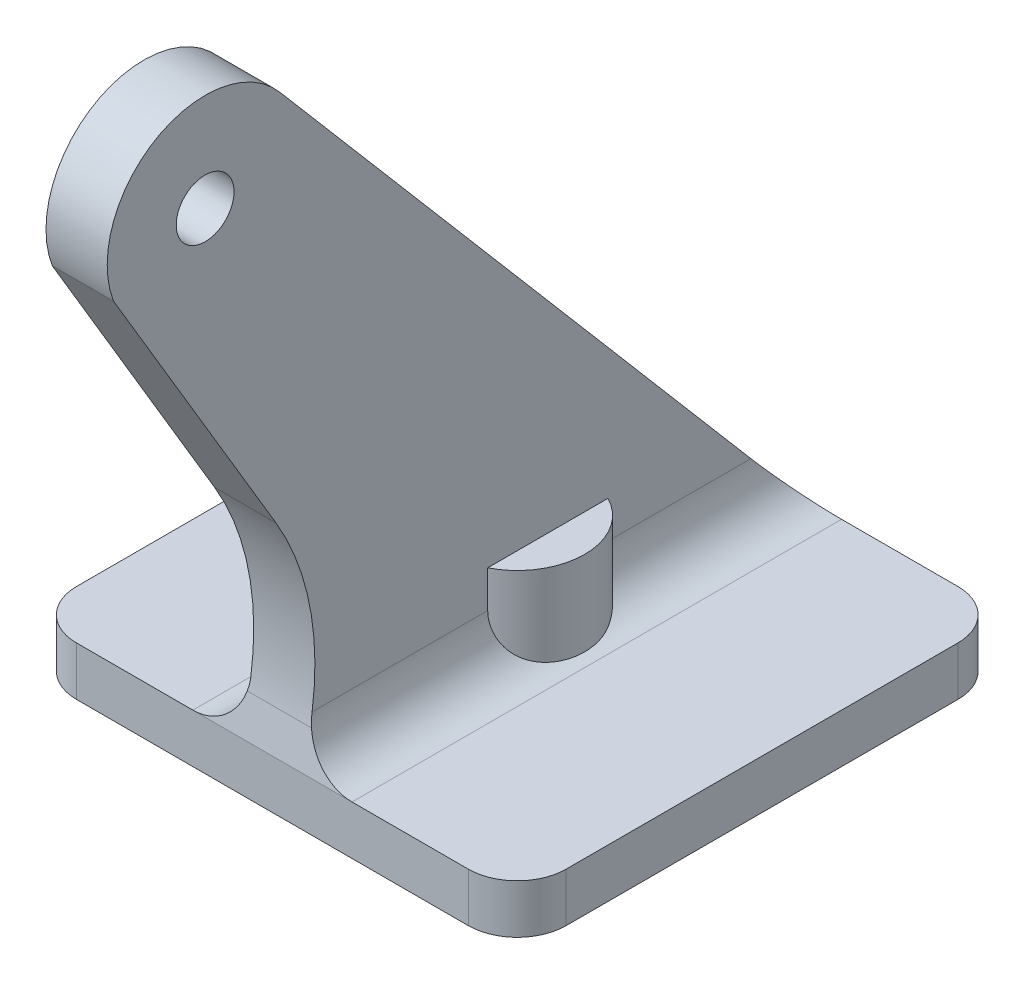
SolidWorks part; units mm, degrees
ref_plane "Front Plane" through (0, 0, 0) normal (0, 0, 1) x (1, 0, 0)
ref_plane "Top Plane" through (0, 0, 0) normal (0, 1, 0) x (1, 0, 0)
ref_plane "Right Plane" through (0, 0, 0) normal (1, 0, 0) x (0, 0, -1)
sketch "Sketch1" plane through (0, 0, 0) normal (0, 1, 0) x (1, 0, 0)
  line L1 (-12.7, 12.7) -> (12.7, 12.7)
  line L2 (-12.7, 12.7) -> (-12.7, -12.7)
  line L3 (-12.7, -12.7) -> (12.7, -12.7)
  line L4 (12.7, 12.7) -> (12.7, -12.7)
  line L5 (-12.7, 12.7) -> (12.7, -12.7) construction
  line L6 (-12.7, -12.7) -> (12.7, 12.7) construction
  point P0 (0, 0)
  dimension "D1" = 25.4
  dimension "D2" = 25.4
extrude "Boss-Extrude1" add sketch "Sketch1" along normal blind 2.54
sketch "Sketch3" plane through (0, 0, 0) normal (1, 0, 0) x (0, 0, -1)
  line L0 (-22.5349, 28.6918) -> (-14.1091, 14.5181)
  line L1 (-13.9132, 33.7746) -> (12.7, 2.54)
  line L2 (12.7, 2.54) -> (-12.7, 2.54)
  line L3 (-12.7, 0) -> (12.7, 0) construction
  line L4 (12.7, 2.54) -> (12.7, 0) construction
  line L5 (-12.3369, 4.4499) -> (-12.7, 2.54)
  arc A0 (-22.5349, 28.6918) -> (-13.9132, 33.7746) centre (-17.78, 30.48) cw
  circle A1 centre (-17.78, 30.48) radius 1.5
  arc A2 (-14.1091, 14.5181) -> (-12.3369, 4.4499) centre (-26.5122, 7.1449) cw
  dimension "D2" = 5.08
  dimension "D3" = 3
  dimension "D1" = 30.48
  dimension "D4" = 30.48
extrude "Boss-Extrude2" add sketch "Sketch3" along normal mid plane 3.175
fillet "Fillet1" radius 2.54 2 edges
fillet "Fillet2" radius 2.54 4 edges at (12.7, 1.27, -12.7) (12.7, 1.27, 12.7) (-12.7, 1.27, 12.7) (-12.7, 1.27, -12.7)
sketch "Sketch4" plane through (0, 0, 0) normal (0, -1, 0) x (1, 0, 0)
  circle A0 centre (0, 0) radius 3.5
  dimension "D1" = 7
extrude "Boss-Extrude3" add sketch "Sketch4" against normal blind 7
sketch "Sketch5" plane through (0, 0, 0) normal (0, -1, 0) x (1, 0, 0)
  circle A0 centre (0, 0) radius 1.25
  dimension "D1" = 2.5
extrude "Cut-Extrude1" cut sketch "Sketch5" against normal blind 6.35
